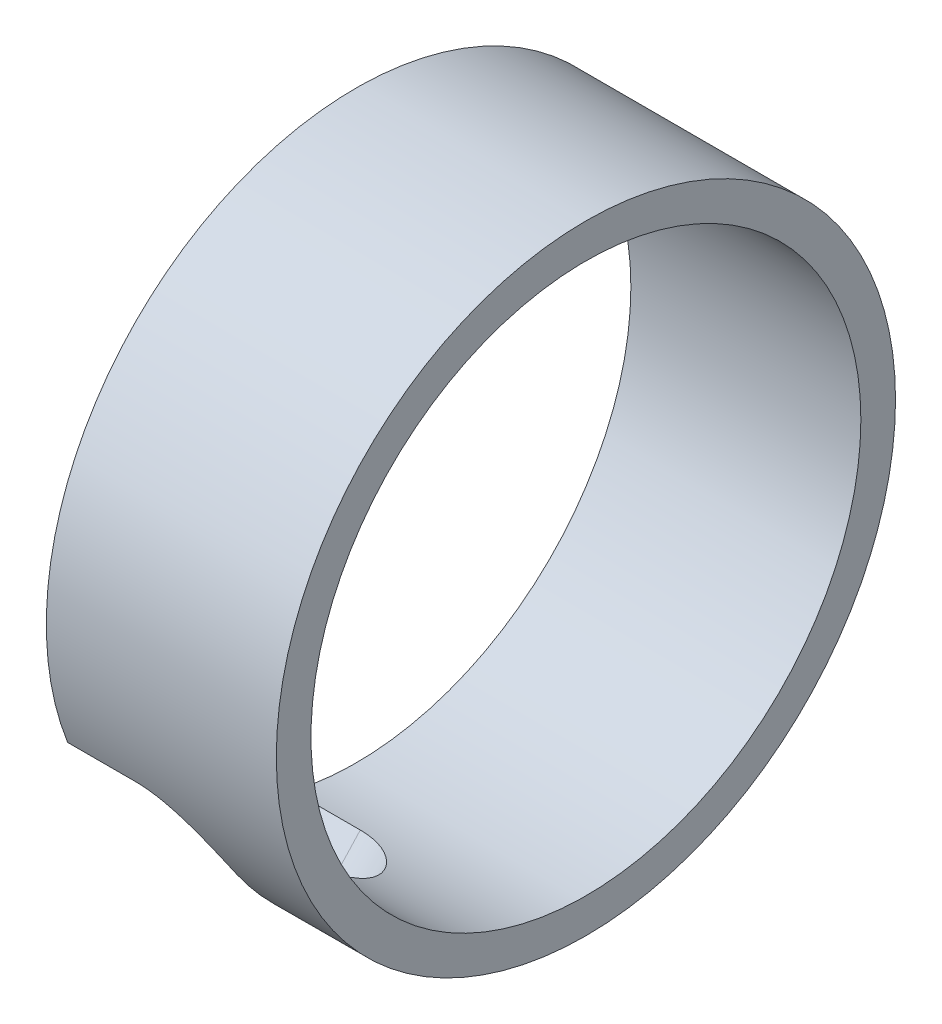
SolidWorks part; units mm, degrees
material "Nylon 6/10"
ref_plane "Front Plane" through (0, 0, 0) normal (0, 0, 1) x (1, 0, 0)
ref_plane "Top Plane" through (0, 0, 0) normal (0, 1, 0) x (1, 0, 0)
ref_plane "Right Plane" through (0, 0, 0) normal (1, 0, 0) x (0, 0, -1)
sketch "Sketch1" plane through (0, 0, 0) normal (0, 0, 1) x (1, 0, 0)
  line L0 (-25.4, 7.5) -> (-42.315, 7.5) construction
  line L1 (-39.013, 8.7312) -> (-32.527, 8.7312)
  line L2 (-39.013, 8.7312) -> (-39.013, 7.754)
  line L3 (-39.013, 7.754) -> (-32.527, 7.754)
  line L4 (-32.527, 8.7312) -> (-32.527, 7.754)
  line L5 (-39.14, -2.5665) -> (-39.14, 3.6316) construction
  line L6 (-32.4, 15.2446) -> (-32.4, -15.2446) construction
  line L7 (0, 0) -> (-47.1489, 0) construction
  dimension "D1" = 0.254
  dimension "D2" = 0.127
  dimension "D3" = 0.127
  dimension "D4" = 17.4625
revolve "Revolve1" add sketch "Sketch1" angle 360 about L7
ref_plane "Plane1" through (0, 0, 0) normal (0, -0.7347, 0.6784) x (1, 0, 0)
sketch "Sketch3" plane through (0, 0, 0) normal (0, -0.7347, 0.6784) x (1, 0, 0)
  line L0 (-39.013, 3.81) -> (-39.013, -3.81)
  line L1 (-39.013, 7.754) -> (-39.013, -7.754) construction
  line L2 (-39.013, -3.81) -> (-37.108, -3.81)
  line L3 (-35.203, -1.905) -> (-35.203, 1.905)
  line L4 (-37.108, 3.81) -> (-39.013, 3.81)
  line L5 (-39.013, 8.7313) -> (-39.013, -8.7312) construction
  line L6 (-39.013, 8.7313) -> (-39.013, -8.7312) construction
  line L7 (-35.203, 0) -> (-39.013, 0) construction
  arc A0 (-37.108, -3.81) -> (-35.203, -1.905) centre (-37.108, -1.905) ccw
  arc A1 (-35.203, 1.905) -> (-37.108, 3.81) centre (-37.108, 1.905) ccw
  dimension "D1" = 7.62
  dimension "D2" = 3.81
extrude "Cut-Extrude1" cut sketch "Sketch3" along normal up to next
